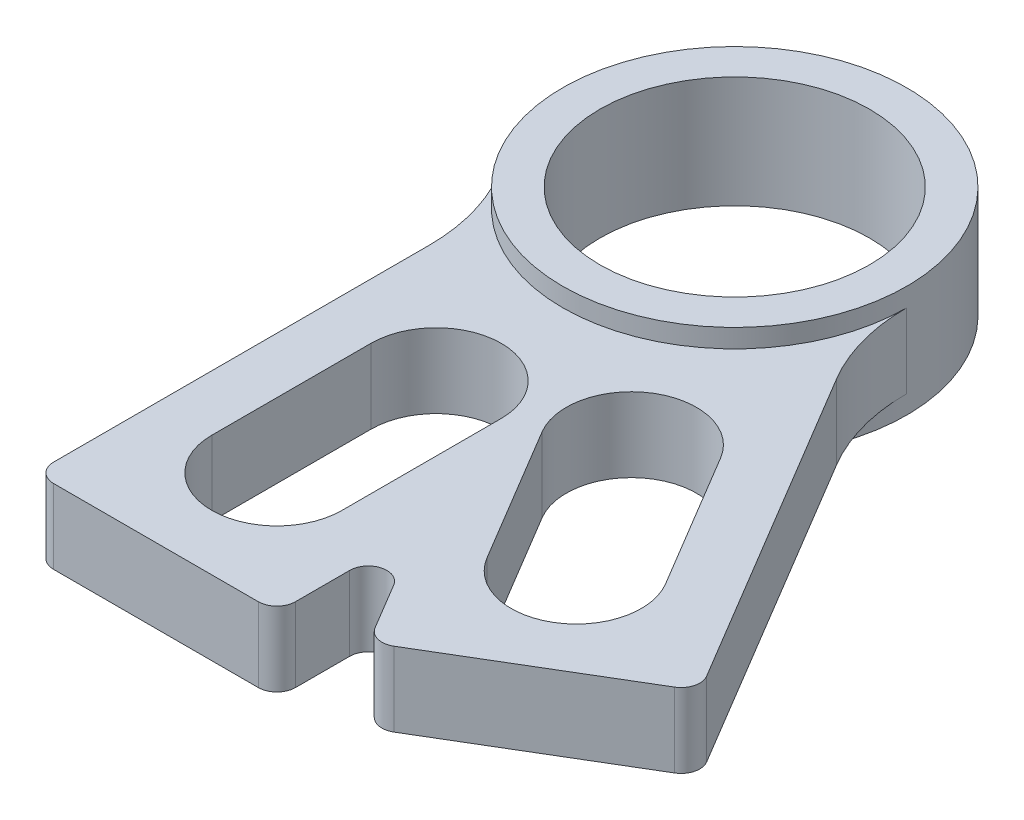
SolidWorks part; units mm, degrees
ref_plane "Front Plane" through (0, 0, 0) normal (0, 0, 1) x (1, 0, 0)
ref_plane "Top Plane" through (0, 0, 0) normal (0, 1, 0) x (1, 0, 0)
ref_plane "Right Plane" through (0, 0, 0) normal (1, 0, 0) x (0, 0, -1)
sketch "Sketch1" plane through (0, 0, 0) normal (0, 1, 0) x (1, 0, 0)
  line L0 (0, 0) -> (0, -49.3903) construction
  line L1 (0, 0) -> (25.3145, -42.4096) construction
  line L2 (0, -39.0716) -> (0, -25.4826) construction
  line L3 (-5.5562, -39.0716) -> (-5.5562, -25.4826)
  line L4 (5.5563, -39.0716) -> (5.5563, -25.4826)
  line L5 (20.0257, -33.5493) -> (13.0608, -21.8809) construction
  line L6 (15.2548, -36.3971) -> (8.2899, -24.7287)
  line L7 (24.7967, -30.7015) -> (17.8318, -19.0331)
  line L8 (0, -49.3903) -> (0, -44.6278) construction
  line L9 (25.3145, -42.4096) -> (22.8735, -38.3203) construction
  line L10 (-10.3187, -49.3903) -> (10.3188, -49.3903)
  line L11 (16.4542, -47.6984) -> (34.1748, -37.1209)
  line L12 (-10.3187, -49.3903) -> (-10.3187, -10.4432)
  line L13 (10.3188, -49.3903) -> (10.3188, -37.4197)
  line L14 (34.1748, -37.1209) -> (14.2129, -3.6784)
  line L15 (16.4542, -47.6984) -> (10.3188, -37.4197)
  line L16 (177.9881, -298.1854) -> (14.7531, -24.7161) construction
  line L22 (0, 0) -> (10.3188, -37.4197) construction
  circle A0 centre (0, 0) radius 11.5062
  circle A1 centre (0, 0) radius 14.6812
  arc A2 (-5.5562, -39.0716) -> (5.5563, -39.0716) centre (0, -39.0716) ccw
  arc A3 (5.5563, -25.4826) -> (-5.5562, -25.4826) centre (0, -25.4826) ccw
  arc A4 (15.2548, -36.3971) -> (24.7967, -30.7015) centre (20.0257, -33.5493) ccw
  arc A5 (17.8318, -19.0331) -> (8.2899, -24.7287) centre (13.0608, -21.8809) ccw
  point P8 (0, -32.2771)
  point P13 (16.5433, -27.7151)
  point P25 (0, -49.3903)
  point P27 (25.3145, -42.4096)
  dimension "D2" = 29.3624
  dimension "D3" = 4.7625
  dimension "D4" = 4.7625
  dimension "D5" = 13.589
  dimension "D6" = 49.3903
  dimension "D7" = 20.6375
extrude "Bearing_Insert_Extrude" add sketch "Sketch1" along normal mid plane 9.525 contours A1 A0 region at (-5.4988, 0, -13.1636)
extrude "Apex_Slot_Insert_Extrude" add sketch "Sketch1<4>" along normal mid plane 6.35 contours A1 L12 L10 L13 L15 L11 L14 A5 L7 A4 L6 A3 L4 A2 L3 region at (8.3224, 0, 30.1803)
sketch "Sketch1<4>" plane through (0, 0, 0) normal (0, 1, 0) x (1, 0, 0) same geometry as "Sketch1"
fillet "Fillet1" radius 16.002 2 edges at (14.2129, 0, 3.6784) (-10.3187, 0, 10.4432)
fillet "Fillet2" radius 1.5875 5 edges at (34.1748, 0, 37.1209) (16.4542, 0, 47.6984) (10.3188, 0, 37.4197) (10.3188, 0, 49.3903) (-10.3187, 0, 49.3903)
equation "\"Apex_thickness\"= .25"
equation "\"Bearing_diameter\"= 0.906in"
equation "\"A-arm_angle\"= 39.1893"
equation "\"D1@Sketch1\"=\"Bearing_diameter\""
equation "\"D1@Apex_Slot_Insert_Extrude\"=\"Apex_thickness\""
